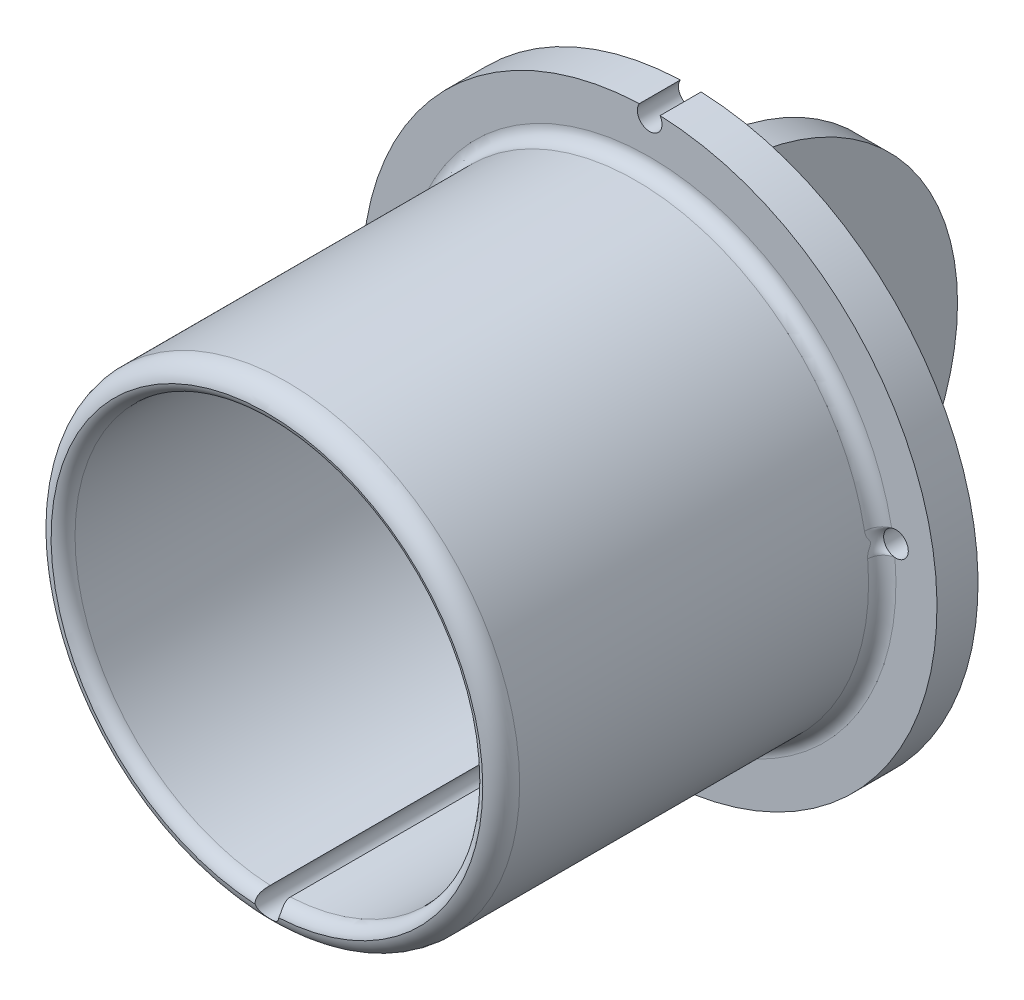
SolidWorks part; units mm, degrees
ref_plane "前视基准面" through (0, 0, 0) normal (0, 0, 1) x (1, 0, 0)
ref_plane "上视基准面" through (0, 0, 0) normal (0, 1, 0) x (1, 0, 0)
ref_plane "右视基准面" through (0, 0, 0) normal (1, 0, 0) x (0, 0, -1)
other "Configuration Table"
sketch "草图2" plane through (0, 0, 0) normal (0, 0, 1) x (1, 0, 0)
  circle A0 centre (0, 0) radius 210
extrude "凸台-拉伸1" add sketch "草图2" along normal blind 30
sketch "草图3" plane through (0, 0, 30) normal (0, 0, 1) x (1, 0, 0)
  circle A0 centre (0, 0) radius 170
  circle A1 centre (0, 0) radius 150
extrude "凸台-拉伸2" add sketch "草图3" along normal blind 280
sketch "草图4" plane through (0, 0, 0) normal (0, 0, -1) x (-1, 0, 0)
sketch "草图5" plane through (0, 0, 0) normal (1, 0, 0) x (0, 0, -1)
  circle A0 centre (0, 0) radius 170
extrude "凸台-拉伸3" add sketch "草图5" along normal blind 25
sketch "草图6" plane through (0, 0, 310) normal (0, 0, 1) x (1, 0, 0)
  circle A0 centre (0, 0) radius 100
sketch "草图7" plane through (0, 0, 0) normal (0, 0, -1) x (-1, 0, 0)
  circle A0 centre (180, 25) radius 9
  circle A1 centre (0, 205) radius 9
  circle A2 centre (-180, 25) radius 9
  circle A3 centre (0, -155) radius 9
extrude "切除-拉伸2" cut sketch "草图7" against normal through all
fillet "圆角1" radius 10 1 edges at (0, 150, 310) tangent propagation no
fillet "圆角2" radius 15 1 edges at (170, 0, 310) tangent propagation no
fillet "圆角3" radius 10 1 edges at (170, 0, 30) tangent propagation no
